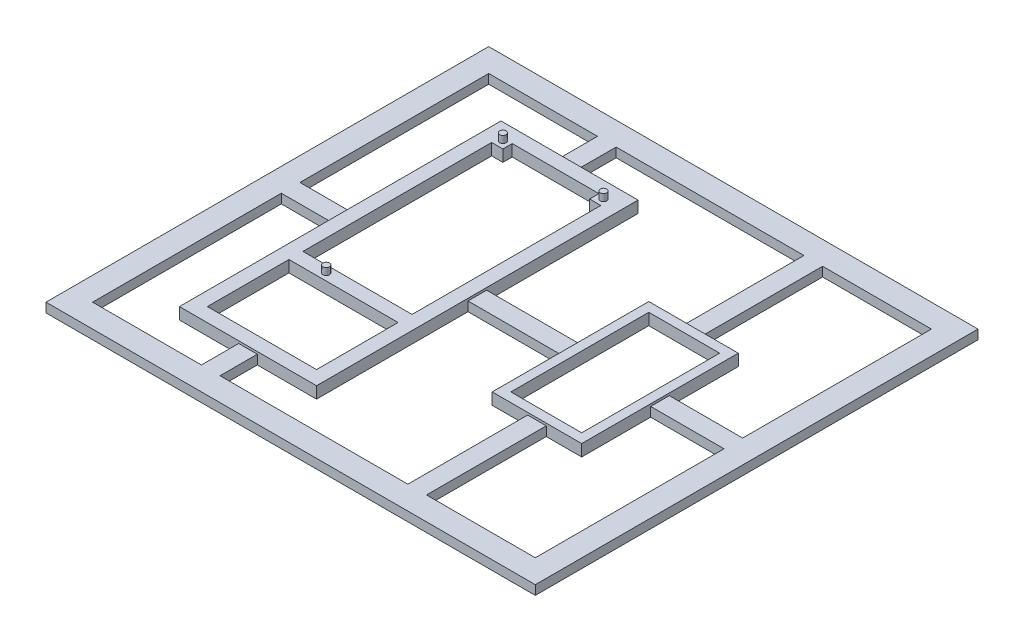
SolidWorks part; units mm, degrees
note: The reader was unsure of these and kept them because the rebuilt part matched: shared geometry of "Sketch2<3>".
ref_plane "Front Plane" through (0, 0, 0) normal (0, 0, 1) x (1, 0, 0)
ref_plane "Top Plane" through (0, 0, 0) normal (0, 1, 0) x (1, 0, 0)
ref_plane "Right Plane" through (0, 0, 0) normal (1, 0, 0) x (0, 0, -1)
sketch "Sketch2" plane through (0, 0, 0) normal (0, 1, 0) x (1, 0, 0)
  line L4 (-55, 0) -> (55, 0) construction
  line L5 (14.71, 29.5) -> (9.3, 29.5)
  line L6 (10.8, 29.5) -> (12.8, 29.5)
  line L7 (-5.21, -12.5) -> (-12.71, -12.5) construction
  line L8 (0, -55) -> (0, 55) construction
  line L9 (-11.71, 31.5) -> (11.71, 31.5)
  line L10 (11.71, -31.5) -> (11.71, 31.5)
  line L11 (-11.71, -31.5) -> (11.71, -31.5)
  line L12 (-11.71, -31.5) -> (-11.71, 31.5)
  line L13 (-14.71, -34.5) -> (-14.71, 34.5)
  line L14 (-14.71, 34.5) -> (14.71, 34.5)
  line L15 (14.71, -34.5) -> (14.71, 34.5)
  line L16 (-14.71, -34.5) -> (14.71, -34.5)
  line L17 (-10.8, 29.5) -> (-12.8, 29.5)
  line L18 (-10.8, 29.5) -> (-10.8, -0.5)
  line L19 (-10.8, -0.5) -> (-12.8, -0.5)
  line L20 (9.3, 34.5) -> (9.3, 29.5)
  line L21 (-14.71, 34.5) -> (-9.3, 34.5)
  line L22 (-14.71, 34.5) -> (-14.71, 29.5)
  line L23 (-14.71, 29.5) -> (-9.3, 29.5)
  line L24 (-9.3, 34.5) -> (-9.3, 29.5)
  line L29 (-12.8, 29.5) -> (-12.8, -0.5)
  line L30 (-14.71, -11) -> (14.71, -11)
  line L31 (-14.71, -11) -> (-14.71, -14)
  line L32 (-14.71, -14) -> (14.71, -14)
  line L33 (14.71, -11) -> (14.71, -14)
  line L34 (12.8, 29.5) -> (12.8, -0.5)
  line L35 (10.8, -0.5) -> (12.8, -0.5)
  line L36 (10.8, 29.5) -> (10.8, -0.5)
  circle A0 centre (-10.8, 31) radius 0.7
  circle A2 centre (-5.21, -12.5) radius 0.7
  circle A3 centre (10.8, 31) radius 0.7
  point P0 (0, 0)
  point P1 (-11.8, 29.5)
  point P33 (0, 0)
  point P41 (0, 0)
  point P42 (0, 0)
  dimension "D3" = 1.4
  dimension "D8" = 1.4
  dimension "D2" = 11.71
  dimension "D4" = 31.5
  dimension "D5" = 23.42
  dimension "D6" = 7.5
  dimension "D7" = 19
  dimension "D11" = 29.42
  dimension "D12" = 34.5
  dimension "D13" = 1.5
  dimension "D14" = 1.5
  dimension "D15" = 1.5
  dimension "D16" = 1.5
  dimension "D9" = 31.5
  dimension "D10" = 9.5
  dimension "D17" = 6.5
  dimension "D18" = 11.71
  dimension "D19" = 3
  dimension "D20" = 2
  dimension "D21" = 30
sketch "Sketch3" plane through (0, 0, 0) normal (0, 1, 0) x (1, 0, 0)
  line L0 (34.71, 16.8) -> (53.91, 16.8)
  line L1 (35.71, -15.8) -> (52.91, -15.8) construction
  line L2 (35.71, -15.8) -> (35.71, 15.8) construction
  line L3 (35.71, 15.8) -> (52.91, 15.8) construction
  line L4 (52.91, -15.8) -> (52.91, 15.8) construction
  line L5 (35.71, -15.8) -> (52.91, 15.8) construction
  line L6 (35.71, 15.8) -> (52.91, -15.8) construction
  line L7 (53.91, -16.8) -> (53.91, 16.8)
  line L8 (34.71, -16.8) -> (53.91, -16.8)
  line L9 (34.71, -16.8) -> (34.71, 16.8)
  line L10 (36.71, 14.8) -> (51.91, 14.8)
  line L11 (51.91, -14.8) -> (51.91, 14.8)
  line L12 (36.71, -14.8) -> (51.91, -14.8)
  line L13 (36.71, -14.8) -> (36.71, 14.8)
  line L14 (14.71, -34.5) -> (14.71, 34.5) construction
  point P0 (44.31, 0)
  point P13 (0, 0)
  point P15 (34.4774, 0)
  dimension "D1" = 31.6
  dimension "D2" = 17.2
  dimension "D5" = 20
  dimension "D3" = 1
  dimension "D4" = 1
extrude "Boss-Extrude1" add sketch "Sketch2" along normal blind 2.5
extrude "Boss-Extrude2" add sketch "Sketch2<3>" along normal blind 4 contours L9 A0 L12 | L9 A0 | A3 L9 | A2
sketch "Sketch2<3>" plane through (0, 0, 0) normal (0, 1, 0) x (1, 0, 0) same geometry as "Sketch2"
extrude "Boss-Extrude3" add sketch "Sketch3" along normal blind 2.5 separate body
sketch "Sketch4" plane through (0, 0, 0) normal (0, 1, 0) x (1, 0, 0)
  line L0 (0, 0) -> (44.31, 0) construction
  line L1 (-27.845, 45) -> (72.155, 45)
  line L2 (-27.845, 45) -> (-27.845, -45)
  line L3 (-27.845, -45) -> (72.155, -45)
  line L4 (72.155, 45) -> (72.155, -45)
  line L5 (-25.345, 42.5) -> (69.655, 42.5)
  line L6 (69.655, 42.5) -> (69.655, -42.5)
  line L7 (-25.345, -42.5) -> (69.655, -42.5)
  line L8 (-25.345, 42.5) -> (-25.345, -42.5)
  line L9 (-14.71, 34.5) -> (14.71, 34.5) construction
  line L10 (-2, 42.5) -> (2, 42.5)
  line L11 (-2, 42.5) -> (-2, 34.5)
  line L12 (-2, 34.5) -> (2, 34.5)
  line L13 (2, 42.5) -> (2, 34.5)
  line L14 (34.71, 16.8) -> (53.91, 16.8) construction
  line L15 (42.31, 16.8) -> (46.31, 16.8)
  line L16 (42.31, 16.8) -> (42.31, 42.5)
  line L17 (42.31, 42.5) -> (46.31, 42.5)
  line L18 (46.31, 16.8) -> (46.31, 42.5)
  line L19 (53.91, -16.8) -> (53.91, 16.8) construction
  line L20 (53.91, 2) -> (69.655, 2)
  line L21 (53.91, 2) -> (53.91, -2)
  line L22 (53.91, -2) -> (69.655, -2)
  line L23 (69.655, 2) -> (69.655, -2)
  line L24 (-14.71, -34.5) -> (-14.71, 34.5) construction
  line L25 (-14.71, 2) -> (-25.345, 2)
  line L26 (-14.71, 2) -> (-14.71, -2)
  line L27 (-14.71, -2) -> (-25.345, -2)
  line L28 (-25.345, 2) -> (-25.345, -2)
  line L29 (-2.2, 0) -> (2.2, 0) construction
  line L30 (-2, -42.5) -> (-2, -34.5)
  line L31 (2, -42.5) -> (2, -34.5)
  line L32 (42.31, -16.8) -> (42.31, -42.5)
  line L33 (46.31, -16.8) -> (46.31, -42.5)
  line L34 (14.71, -34.5) -> (14.71, 34.5) construction
  line L35 (14.71, 2) -> (34.71, 2)
  line L36 (14.71, 2) -> (14.71, -2)
  line L37 (14.71, -2) -> (34.71, -2)
  line L38 (34.71, 2) -> (34.71, -2)
  line L39 (34.71, 16.8) -> (34.71, -16.8) construction
  line L40 (-2, -34.5) -> (2, -34.5)
  line L41 (42.31, -16.8) -> (46.31, -16.8)
  line L42 (-30.345, 47.5) -> (-30.345, -47.5)
  line L43 (-30.345, -47.5) -> (74.655, -47.5)
  line L44 (74.655, 47.5) -> (74.655, -47.5)
  line L45 (-30.345, 47.5) -> (74.655, 47.5)
  point P4 (-27.845, 0)
  point P5 (22.155, 0)
  point P10 (22.155, 45)
  point P39 (0, 34.5)
  point P40 (-14.71, 0)
  point P41 (44.31, 16.8)
  point P42 (53.91, 0)
  point P61 (14.71, 0)
  dimension "D1" = 100
  dimension "D2" = 90
  dimension "D4" = 4
  dimension "D5" = 4
  dimension "D6" = 4
  dimension "D7" = 4
  dimension "D8" = 4
  dimension "D3" = 2.5
  dimension "D9" = 2.5
extrude "Boss-Extrude4" add sketch "Sketch4" along normal blind 2 contours L40 L30 L7 L31 | L41 L32 L7 L33 | L4 L1 L2 L3 L8 L5 L6 L7 | L21 L22 L6 L20 | L36 L0 L38 L35 | L27 L26 L25 L8 | L13 L5 L11 L12 | L45 L42 L43 L44 L1 L4 L3 L2 | L16 L17 L18 L15
